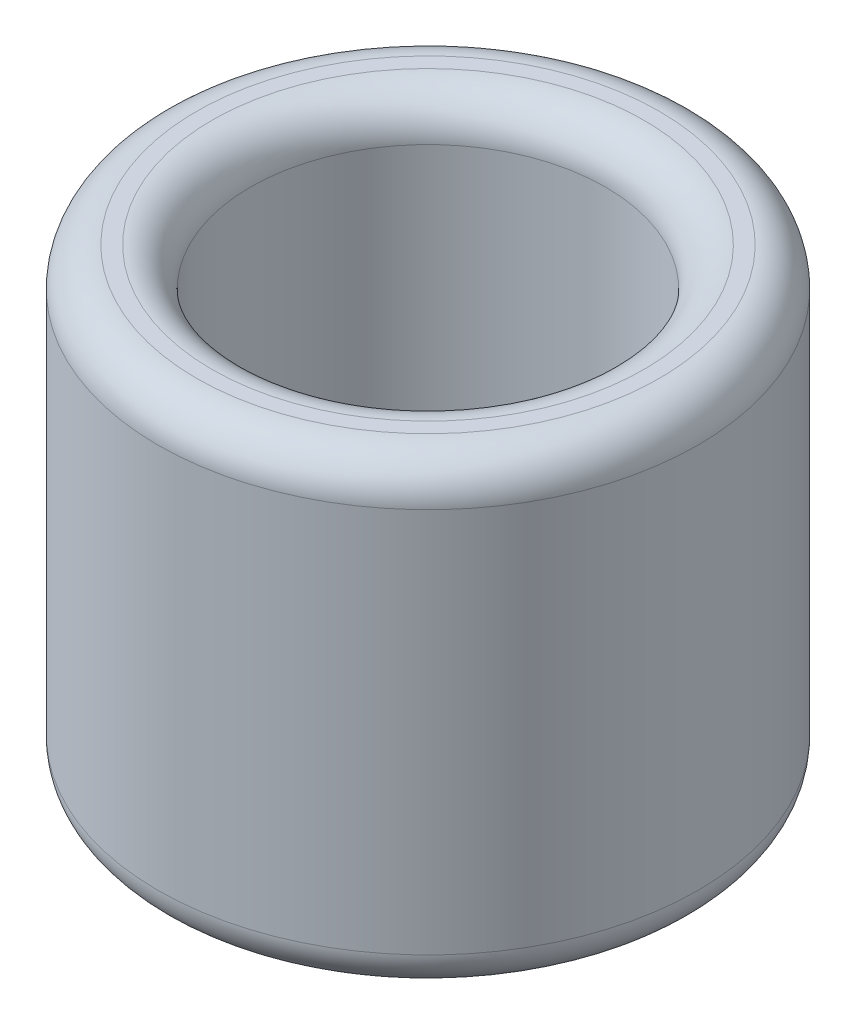
SolidWorks part; units mm, degrees
ref_plane "Front Plane" through (0, 0, 0) normal (0, 0, 1) x (1, 0, 0)
ref_plane "Top Plane" through (0, 0, 0) normal (0, 1, 0) x (1, 0, 0)
ref_plane "Right Plane" through (0, 0, 0) normal (1, 0, 0) x (0, 0, -1)
sketch "Sketch1" plane through (0, 0, 0) normal (0, 1, 0) x (1, 0, 0)
  circle A0 centre (0, 0) radius 1.15
  circle A1 centre (0, 0) radius 1.75
  dimension "D1" = 2.3
  dimension "D2" = 3.5
extrude "Boss-Extrude1" add sketch "Sketch1" along normal blind 3
fillet "Fillet1" radius 0.25 4 edges at (0, 0, 1.15) (0, 0, 1.75) (0, 3, 1.15) (0, 3, 1.75)
